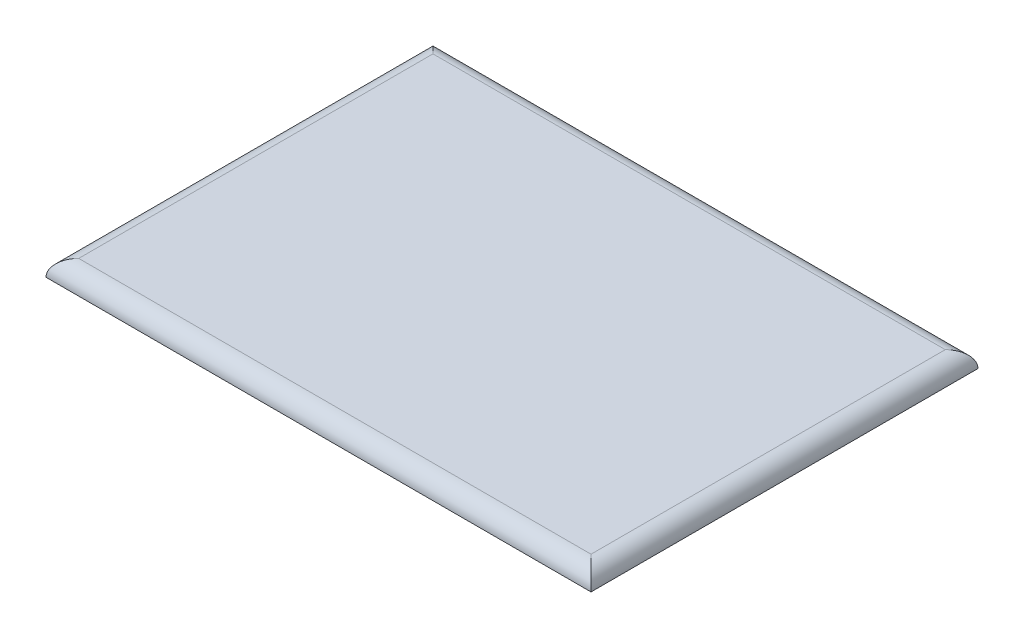
SolidWorks part; units mm, degrees
ref_plane "Front Plane" through (0, 0, 0) normal (0, 0, 1) x (1, 0, 0)
ref_plane "Top Plane" through (0, 0, 0) normal (0, 1, 0) x (1, 0, 0)
ref_plane "Right Plane" through (0, 0, 0) normal (1, 0, 0) x (0, 0, -1)
sketch "Sketch1" plane through (0, 0, 0) normal (0, 1, 0) x (1, 0, 0)
  line L1 (-54.7834, 37.8189) -> (45.2166, 37.8189)
  line L2 (-54.7834, 37.8189) -> (-54.7834, -33.1811)
  line L3 (-54.7834, -33.1811) -> (45.2166, -33.1811)
  line L4 (45.2166, 37.8189) -> (45.2166, -33.1811)
extrude "Boss-Extrude1" add sketch "Sketch1" along normal blind 3
sketch "Sketch2" plane through (0, 3, 0) normal (0, 1, 0) x (1, 0, 0)
  line L0 (45.2166, -33.1811) -> (45.2166, -28.1811) construction
  line L1 (45.2166, -33.1811) -> (45.2166, 37.8189) construction
  line L2 (45.2166, -28.1811) -> (40.2166, -28.1811) construction
fillet "Fillet4" radius 3 4 edges at (-4.7834, 3, -37.8189) (45.2166, 3, -2.3189) (-4.7834, 3, 33.1811) (-54.7834, 3, -2.3189)
